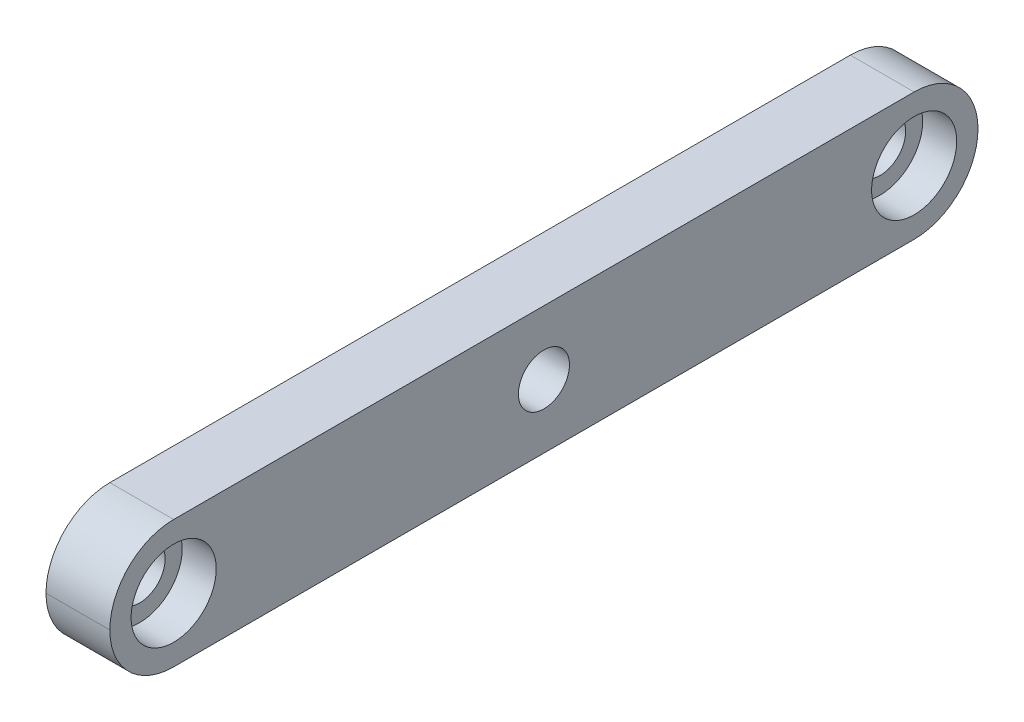
SolidWorks part; units mm, degrees
ref_plane "前视基准面" through (0, 0, 0) normal (0, 0, 1) x (1, 0, 0)
ref_plane "上视基准面" through (0, 0, 0) normal (0, 1, 0) x (1, 0, 0)
ref_plane "右视基准面" through (0, 0, 0) normal (1, 0, 0) x (0, 0, -1)
other "Configuration Table"
sketch "草图1" plane through (0, 0, 0) normal (1, 0, 0) x (0, 0, -1)
  line L5 (-10.2, 1.5) -> (10.2, 1.5)
  line L6 (-10.2, 1.5) -> (-10.2, -1.5)
  line L7 (-10.2, -1.5) -> (10.2, -1.5)
  line L8 (10.2, 1.5) -> (10.2, -1.5)
  circle A3 centre (0, 0) radius 0.6
  circle A4 centre (-8.7, 0) radius 0.6
  circle A5 centre (8.7, 0) radius 0.6
  circle A6 centre (-8.7, 0) radius 1
  circle A7 centre (8.7, 0) radius 1
  dimension "D1" = 8.7
  dimension "D3" = 1.2
  dimension "D8" = 2
  dimension "D2" = 8.7
  dimension "D4" = 1.5
  dimension "D5" = 1.5
  dimension "D6" = 1.5
  dimension "D7" = 1.5
extrude "凸台-拉伸1" add sketch "草图1" along normal blind 1.5 contours L7 L8 L5 L6 | A4 | A3 | A5
fillet "圆角1" radius 1.5 4 edges at (0.75, -1.5, -10.2) (0.75, 1.5, -10.2) (0.75, -1.5, 10.2) (0.75, 1.5, 10.2)
extrude "切除-拉伸1" cut sketch "草图1<3>" against normal blind 0.8 from surface contours A6 | A7 starting at face at (1.5, 0, -0.6)
sketch "草图1<3>" plane through (0, 0, 0) normal (1, 0, 0) x (0, 0, -1) same geometry as "草图1"
